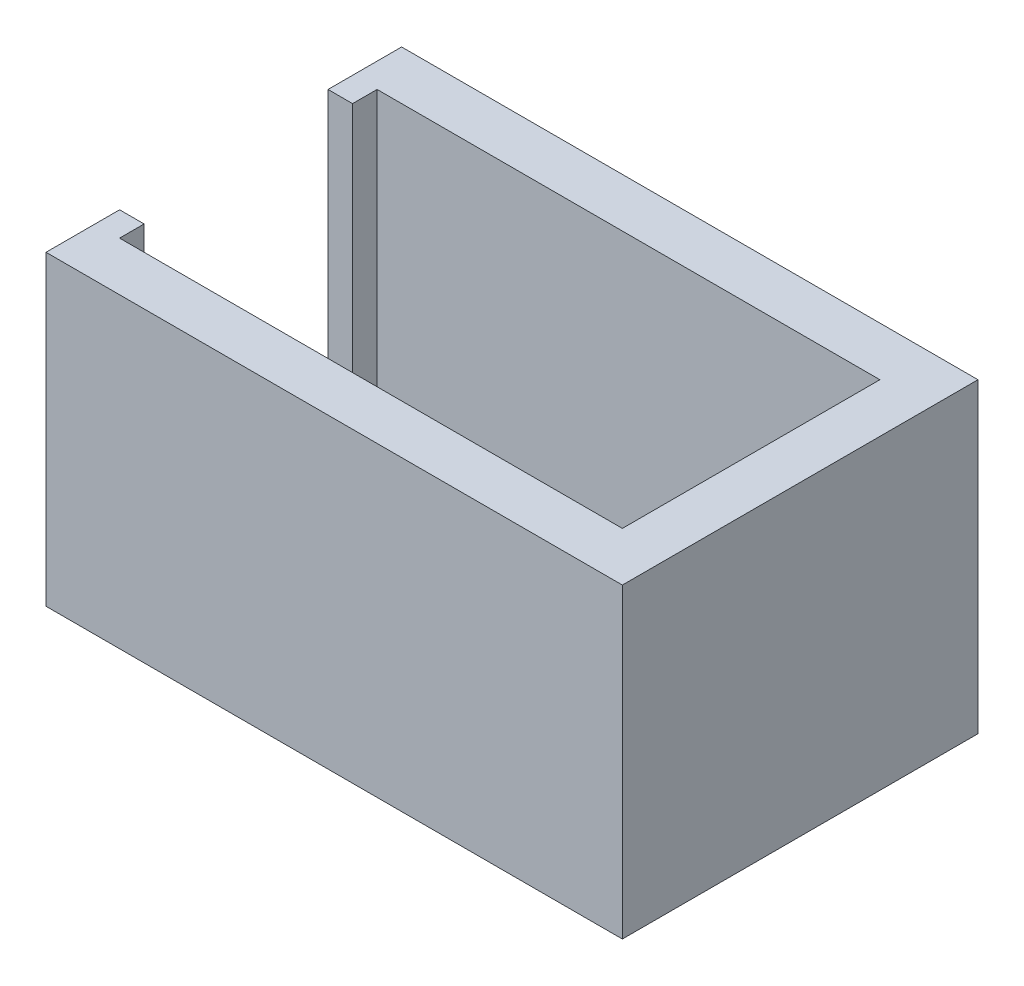
SolidWorks part; units mm, degrees
ref_plane "Front Plane" through (0, 0, 0) normal (0, 0, 1) x (1, 0, 0)
ref_plane "Top Plane" through (0, 0, 0) normal (0, 1, 0) x (1, 0, 0)
ref_plane "Right Plane" through (0, 0, 0) normal (1, 0, 0) x (0, 0, -1)
sketch "Sketch1" plane through (0, 0, 0) normal (0, 1, 0) x (1, 0, 0)
  line L0 (-49.53, 13.335) -> (-49.53, 18.415)
  line L1 (-49.53, -13.335) -> (-5.08, -13.335)
  line L3 (-49.53, 13.335) -> (-5.08, 13.335)
  line L4 (49.53, -13.335) -> (49.53, 13.335)
  line L5 (-49.53, -13.335) -> (49.53, 13.335) construction
  line L6 (-49.53, 13.335) -> (49.53, -13.335) construction
  line L7 (-49.53, -18.415) -> (54.61, -18.415)
  line L9 (-49.53, 18.415) -> (54.61, 18.415)
  line L10 (54.61, -18.415) -> (54.61, 18.415)
  line L11 (-49.53, -16.702) -> (54.61, 18.415) construction
  line L12 (-49.53, 16.702) -> (54.61, -18.415) construction
  line L13 (-49.53, -13.335) -> (-49.53, -18.415)
  line L14 (49.53, 0) -> (-49.53, 0) construction
  line L15 (-5.08, -13.335) -> (-5.08, -10.7928)
  line L16 (-5.08, -10.7928) -> (-2.54, -10.7928)
  line L17 (-2.54, -10.7928) -> (-2.54, -13.335)
  line L18 (-2.54, 10.7928) -> (-2.54, 13.335)
  line L19 (-5.08, 10.7928) -> (-2.54, 10.7928)
  line L20 (-5.08, 13.335) -> (-5.08, 10.7928)
  line L21 (-2.54, 13.335) -> (49.53, 13.335)
  line L22 (-2.54, -13.335) -> (49.53, -13.335)
  point P0 (0, 0)
  point P6 (0, 0)
  dimension "D1" = 99.06
  dimension "D2" = 26.67
  dimension "D3" = 5.08
  dimension "D4" = 5.08
  dimension "D5" = 5.08
  dimension "D6" = 2.54
  dimension "D7" = 52.07
extrude "Boss-Extrude1" add sketch "Sketch1" along normal blind 26.67
sketch "Sketch12" plane through (0, 0, 0) normal (0, -1, 0) x (1, 0, 0)
  line L1 (-49.53, 18.415) -> (54.61, 18.415)
  line L2 (-49.53, 18.415) -> (-49.53, -18.415)
  line L3 (-49.53, -18.415) -> (54.61, -18.415)
  line L4 (54.61, 18.415) -> (54.61, -18.415)
extrude "Boss-Extrude2" add sketch "Sketch12" along normal blind 5.08
sketch "Sketch14" plane through (0, 26.67, 0) normal (0, 1, 0) x (1, 0, 0)
  line L0 (-5.08, 13.335) -> (-5.08, -13.335) construction
  line L1 (54.61, 18.415) -> (-49.53, 18.415) construction
  line L2 (-5.08, 18.415) -> (-49.53, 18.415)
  line L3 (-5.08, 18.415) -> (-5.08, -18.415)
  line L4 (-5.08, -18.415) -> (-49.53, -18.415)
  line L5 (-49.53, 18.415) -> (-49.53, -18.415)
extrude "Cut-Extrude1" cut sketch "Sketch14" against normal through all both and the other way through all
